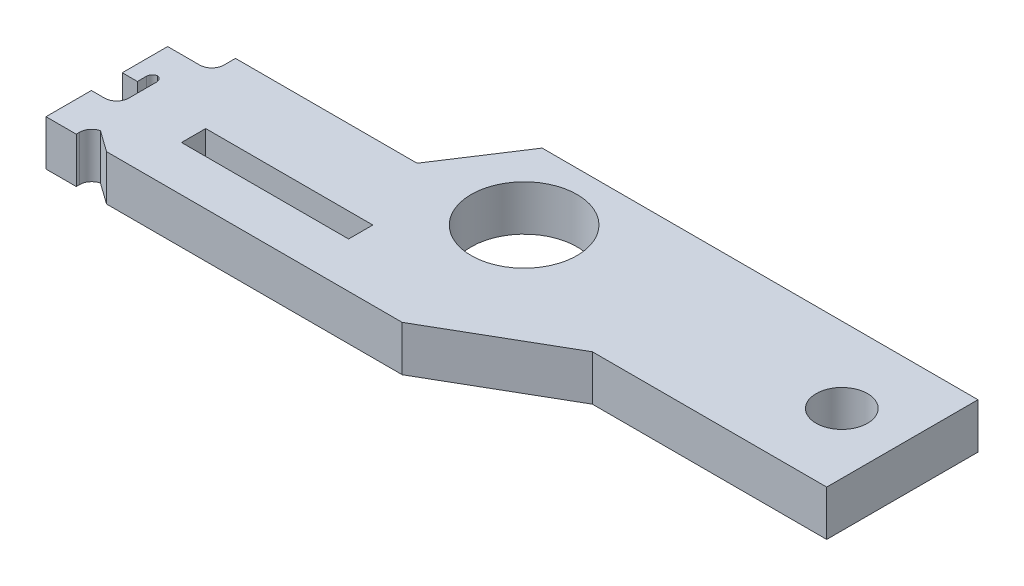
SolidWorks part; units mm, degrees
ref_plane "前视基准面" through (0, 0, 0) normal (0, 0, 1) x (1, 0, 0)
ref_plane "上视基准面" through (0, 0, 0) normal (0, 1, 0) x (1, 0, 0)
ref_plane "右视基准面" through (0, 0, 0) normal (1, 0, 0) x (0, 0, -1)
sketch "草图2" plane through (0, 7.0968, 0) normal (0, 1, 0) x (1, 0, 0)
  line L0 (-1.9, 0) -> (-7.4223, 0)
  line L2 (-1.9, 0) -> (-1.9, 0.8)
  line L3 (-1.9, 0.8) -> (-7.4223, 0.8) construction
  line L5 (-10.4, 0) -> (-10.4, -1.5)
  line L6 (-10.4, -1.5) -> (-9.4, -1.5)
  line L7 (13.1, 0.8) -> (13.1, 5.8)
  line L8 (-9.4, -1) -> (-9.1, -1)
  line L9 (-9.1, -1) -> (-8.4, -1.5)
  line L10 (-1.3034, 5.8) -> (-2.9368, 3.3)
  line L11 (13.1, 5.8) -> (-1.3034, 5.8)
  line L12 (-10.3979, 3.3) -> (-10.3979, 0.8) construction
  line L13 (-9.4, -1.5) -> (-9.4, -1)
  line L14 (-8.938, 3.3) -> (-8.938, 2.5181)
  line L15 (1.3718, -1.5) -> (5.3555, 0.8)
  line L16 (5.3555, 0.8) -> (13.1, 0.8)
  line L17 (-8.4, -1.5) -> (1.3718, -1.5)
  line L18 (-2.9368, 3.3) -> (-10.3979, 3.3) construction
  line L19 (-8.938, 2.5181) -> (-10.3979, 2.5181)
  line L20 (-10.3979, 2.5181) -> (-10.3979, 1.0181)
  line L21 (-7.4223, 0) -> (-7.4223, 0.8)
  line L22 (-10.3979, 1.0181) -> (-9.8979, 1.0181)
  line L23 (-9.8979, 1.0181) -> (-9.8979, 1.5181)
  line L24 (-9.8979, 1.5181) -> (-9.5635, 1.5181)
  line L25 (-9.5635, 1.5181) -> (-9.5635, 0.8)
  line L26 (-2.9368, 3.3) -> (-8.938, 3.3)
  line L27 (-7.4223, 0.8) -> (-1.9, 0.8)
  line L28 (-9.5635, 0.8) -> (-9.5635, 0)
  line L29 (-9.5635, 0) -> (-10.4, 0)
  line L30 (-9.5635, 0.8) -> (-10.3979, 0.8) construction
  circle A0 centre (11.1, 3.3) radius 0.85
  circle A1 centre (0.6, 3.3) radius 1.75
  dimension "D4" = 1.7
  dimension "D5" = 3.5
  dimension "D2" = 1.5
  dimension "D6" = 10.5
  dimension "D7" = 1
  dimension "D8" = 2.5
  dimension "D10" = 10
  dimension "D12" = 1
  dimension "D13" = 2
  dimension "D14" = 30
  dimension "D3" = 5
  dimension "D16" = 0.3
  dimension "D11" = 1
  dimension "D17" = 1.5
  dimension "D18" = 0.5
extrude "凸台-拉伸1" add sketch "草图2" against normal blind 1.5
fillet "Fillet2" radius 0.4 1 edges at (-9.5635, 6.3468, 0)
fillet "Fillet3" radius 0.2 2 edges at (-9.8979, 6.3468, -1.5181) (-9.5635, 6.3468, -1.5181)
fillet "Fillet5" radius 0.4 2 edges at (-9.4, 6.3468, 1) (-8.938, 6.3468, -2.5181)
equation "\"D8@草图2\"=\"D3@草图2\"/2"
